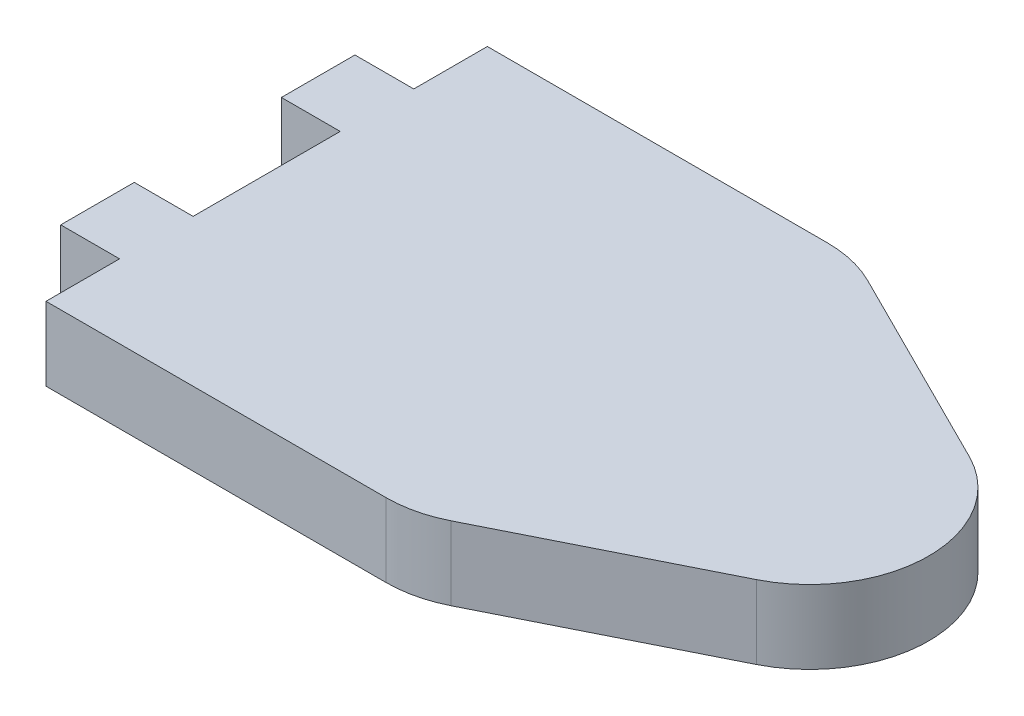
SolidWorks part; units mm, degrees
ref_plane "Front Plane" through (0, 0, 0) normal (0, 0, 1) x (1, 0, 0)
ref_plane "Top Plane" through (0, 0, 0) normal (0, 1, 0) x (1, 0, 0)
ref_plane "Right Plane" through (0, 0, 0) normal (1, 0, 0) x (0, 0, -1)
sketch "Sketch1" plane through (0, 0, 0) normal (0, 1, 0) x (1, 0, 0)
  line L0 (0, 0) -> (0, 10)
  line L13 (0, 10) -> (-8, 10)
  line L14 (-8, 10) -> (-8, 20)
  line L16 (-8, 20) -> (0, 20)
  line L17 (0, 20) -> (0, 40)
  line L18 (0, 40) -> (-8, 40)
  line L19 (-8, 40) -> (-8, 50)
  line L20 (-8, 50) -> (0, 50)
  line L21 (0, 50) -> (0, 60)
  line L22 (0, 60) -> (50, 60)
  line L23 (50, 60) -> (90, 40)
  line L24 (90, 40) -> (90, 20)
  line L25 (90, 20) -> (50, 0)
  line L26 (50, 0) -> (0, 0)
  dimension "D1" = 10
  dimension "D2" = 10
  dimension "D3" = 20
  dimension "D4" = 10
  dimension "D5" = 10
  dimension "D6" = 8
  dimension "D7" = 8
  dimension "D8" = 50
  dimension "D9" = 40
  dimension "D10" = 50
  dimension "D11" = 20
  dimension "D12" = 20
extrude "Boss-Extrude2" add sketch "Sketch1" along normal blind 10
sketch "Sketch5" plane through (0, 10, 0) normal (0, 1, 0) x (1, 0, 0)
  line L0 (90, 40) -> (50, 60) construction
  line L1 (50, 0) -> (90, 20) construction
  line L2 (90, 20) -> (90, 40) construction
  line L3 (81.0557, 44.4721) -> (90, 40)
  line L4 (90, 40) -> (90, 20)
  line L5 (90, 20) -> (81.0557, 15.5279)
  arc A0 (81.0557, 44.4721) -> (81.0557, 15.5279) centre (73.8197, 30) cw
  line M2 (50, 0) -> (90, 20)
  line M3 (90, 20) -> (90, 40)
  line M4 (90, 40) -> (50, 60)
extrude "Cut-Extrude2" cut sketch "Sketch5" against normal blind 10 contours A0 L4 M4 | A0 M3 M2 region at (88.1125, 10, -21.1665) region at (88.1125, 10, -38.8335)
fillet "Fillet3" radius 16 2 edges at (50, 5, -60) (50, 5, 0)
